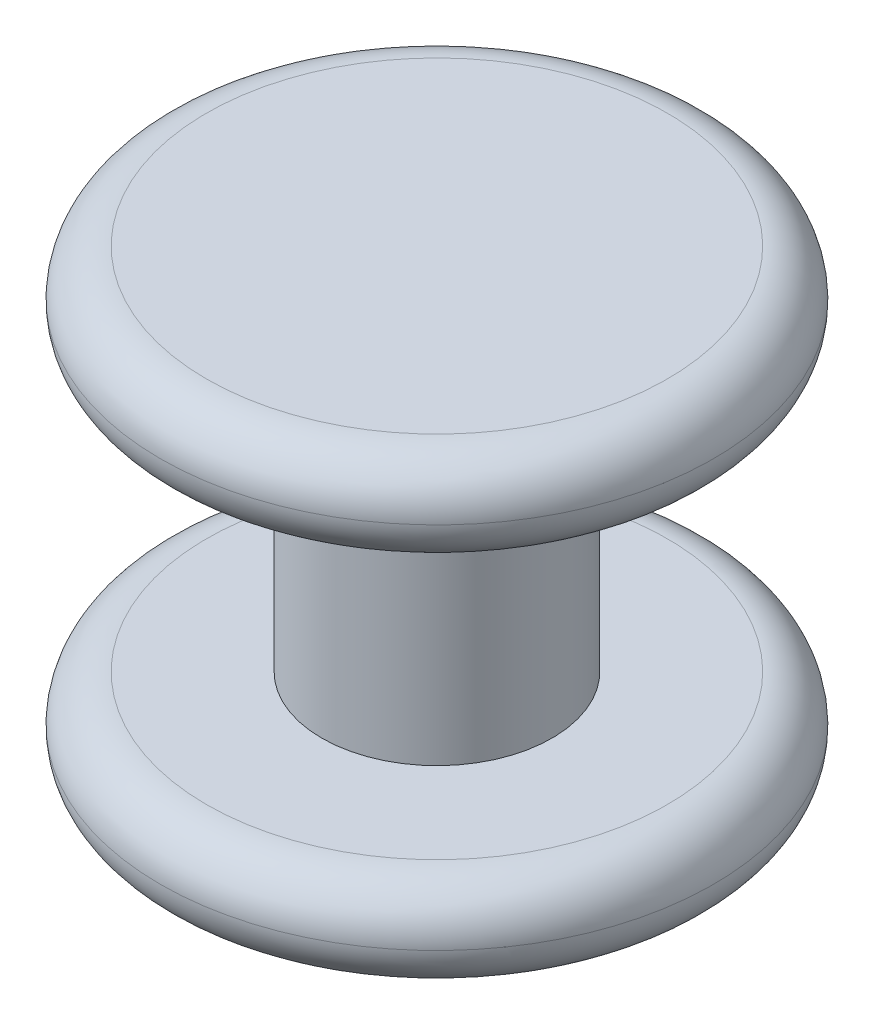
SolidWorks part; units mm, degrees
material "1060 Alloy"
ref_plane "Front Plane" through (0, 0, 0) normal (0, 0, 1) x (1, 0, 0)
ref_plane "Top Plane" through (0, 0, 0) normal (0, 1, 0) x (1, 0, 0)
ref_plane "Right Plane" through (0, 0, 0) normal (1, 0, 0) x (0, 0, -1)
sketch "Sketch1" plane through (0, 0, 0) normal (0, 1, 0) x (1, 0, 0)
  circle A0 centre (0, 0) radius 2.5
  dimension "D1" = 5
extrude "Boss-Extrude1" add sketch "Sketch1" along normal blind 3
sketch "Sketch2" plane through (0, 3, 0) normal (0, 1, 0) x (1, 0, 0)
  circle A3 centre (0, 0) radius 6
  dimension "D1" = 12
extrude "Boss-Extrude2" add sketch "Sketch2" along normal blind 2
fillet "Fillet1" radius 1 2 edges at (0, 5, 6) (0, 3, 6)
mirror "Mirror1" about plane through (0, 0, 0) normal (0, 1, 0) of bodies 102
